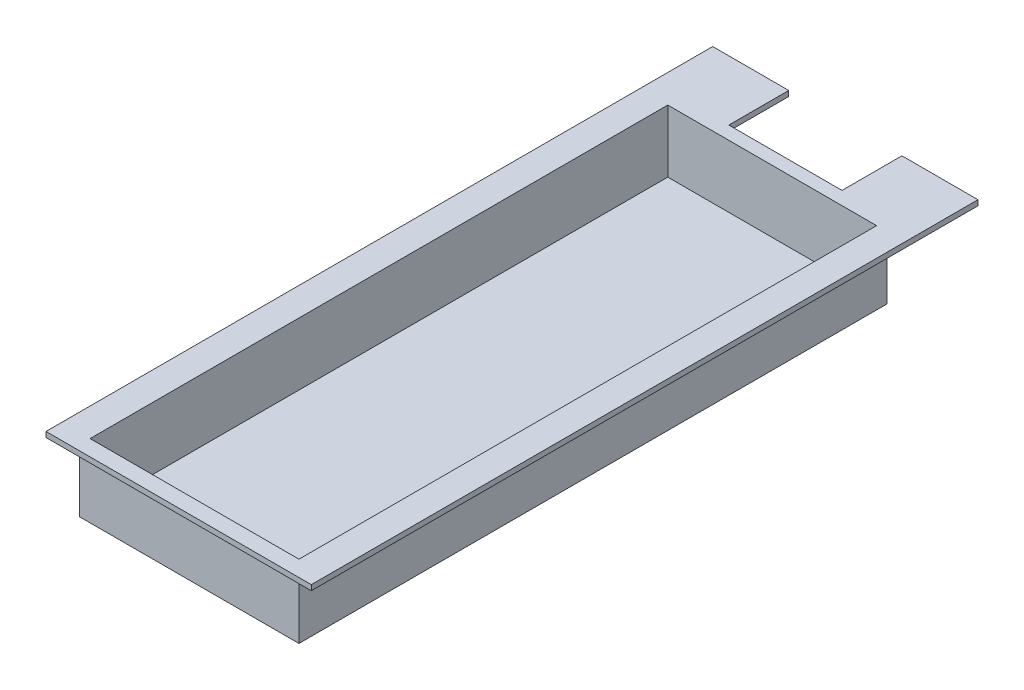
SolidWorks part; units mm, degrees
ref_plane "Front Plane" through (0, 0, 0) normal (0, 0, 1) x (1, 0, 0)
ref_plane "Top Plane" through (0, 0, 0) normal (0, 1, 0) x (1, 0, 0)
ref_plane "Right Plane" through (0, 0, 0) normal (1, 0, 0) x (0, 0, -1)
sketch "Sketch1" plane through (0, 0, 0) normal (0, 1, 0) x (1, 0, 0)
  line L2 (63.8696, 121.7466) -> (63.8696, -211.8735)
  line L3 (63.8696, -211.8735) -> (188.3296, -211.8735)
  line L4 (188.3296, 121.7466) -> (188.3296, -211.8735)
  line L7 (87.9996, 121.7466) -> (63.8696, 121.7466)
  line L8 (87.9996, 121.7466) -> (164.1996, 121.7466)
  line L11 (164.1996, 121.7466) -> (188.3296, 121.7466)
  dimension "D5" = 124.46
  dimension "D6" = 76.2
base flange "Base-Flange1" sketch "Sketch1" thickness 3 reverse thickness direction no parameters "D1"=9
ref_plane "Plane3" through (0, 0, 0) normal (0, 1, 0) x (1, 0, 0)
sketch "Sketch75" plane through (0, 0, 0) normal (0, 1, 0) x (1, 0, 0)
  line L0 (63.8696, -211.8735) -> (188.3296, -211.8735) construction
  line L2 (63.8696, 121.7466) -> (63.8696, -211.8735)
  line L3 (63.8696, -211.8735) -> (66.8696, -211.8735)
  line L5 (167.1996, 118.7466) -> (185.3296, 118.7466)
  line L6 (164.1996, 121.7466) -> (185.3296, 121.7466)
  line L8 (66.8696, -208.8735) -> (185.3296, -208.8735)
  line L10 (66.8696, -211.8735) -> (188.3296, -211.8735)
  line L11 (188.3296, -193.287) -> (188.3296, -211.8735)
  line L12 (188.3296, 121.7466) -> (63.8696, 121.7466) construction
  line L13 (84.9996, 118.7466) -> (66.8696, 118.7466)
  line L18 (87.9996, 121.7466) -> (63.8696, 121.7466)
  line L19 (66.8696, 118.7466) -> (66.8696, -208.8735)
  line L20 (188.3296, -193.287) -> (188.3296, 121.7466)
  line L21 (87.9996, 121.7466) -> (164.1996, 121.7466)
  line L23 (87.9996, 118.7466) -> (164.1996, 118.7466)
  line L25 (188.3296, 121.7466) -> (185.3296, 121.7466)
  line L29 (87.9996, 118.7466) -> (84.9996, 118.7466)
  line L35 (164.1996, 118.7466) -> (167.1996, 118.7466)
  line L48 (185.3296, 118.7466) -> (185.3296, -208.8735)
  point P4 (65.3696, -21.027)
  point P11 (127.5996, -194.787)
  point P39 (186.8296, -21.027)
  dimension "D2" = 3
  dimension "D4" = 3
extrude "Boss-Extrude1" add sketch "Sketch75" along normal blind 35.4 contours L20 L25 L6 L21 L18 L2 L3 L10 L11 L5 L48 L8 L19 L13 L29 L23 L35
ref_plane "Plane4" through (0, 35.4, 0) normal (0, 1, 0) x (1, 0, 0)
sketch "Sketch76" plane through (0, 35.4, 0) normal (0, 1, 0) x (1, 0, 0)
  line L0 (164.1996, 121.7466) -> (87.9996, 121.7466) construction
  line L3 (168.6072, 160.233) -> (188.3296, 160.233)
  line L5 (63.8696, -211.8735) -> (188.3296, -211.8735) construction
  line L6 (63.8696, 121.7466) -> (87.9996, 121.7466)
  line L7 (168.6072, 160.233) -> (158.1996, 160.233)
  line L9 (164.1996, 121.7466) -> (142.9989, 121.7466)
  line L10 (158.1996, 160.233) -> (158.1996, 126.2466)
  line L11 (164.1996, 121.7466) -> (188.3296, 121.7466)
  line L12 (63.8696, 121.7466) -> (63.8696, -211.8735)
  line L13 (188.3296, -211.8735) -> (188.3296, 121.7466)
  line L14 (158.1996, 126.2466) -> (93.9996, 126.2466)
  line L16 (142.9989, 121.7466) -> (87.9996, 121.7466)
  line L23 (93.9996, 154.233) -> (93.9996, 126.2466)
  line L28 (61.1738, 160.233) -> (93.9996, 160.233)
  line L29 (93.9996, 154.233) -> (93.9996, 160.233)
  line L32 (61.1738, 160.233) -> (50.8696, 160.233)
  line L35 (50.8696, 160.233) -> (50.8696, -212.8408)
  line L38 (50.8696, 160.233) -> (61.1738, 160.233)
  line L39 (63.8696, -211.8735) -> (188.3296, -211.8735)
  line L40 (50.8696, -212.8408) -> (50.8696, -217.8735)
  line L41 (50.8696, -217.8735) -> (190.3296, -217.8735)
  line L45 (188.3296, 160.233) -> (201.3296, 160.233)
  line L47 (190.3296, -217.8735) -> (201.3296, -217.8735)
  line L48 (201.3296, 160.233) -> (201.3296, -217.8735)
  dimension "D1" = 13
  dimension "D2" = 6
  dimension "D3" = 4.5
  dimension "D4" = 13
  dimension "D5" = 43.13
  dimension "D6" = 43.13
extrude "Boss-Extrude2" add sketch "Sketch76" against normal blind 3
sketch "Bend-Lines1" [suppressed] plane through (0, 0, 0) normal (0, 1, 0) x (1, 0, 0)
sketch "Bounding-Box1" [suppressed] plane through (0, 0, 0) normal (0, 1, 0) x (1, 0, 0)
sheet metal parameters "Sheet-Metal4" thickness 3 parameters "D1"=9
flat pattern "Flat-Pattern4" [suppressed]
sketch "Bend-Lines2" plane through (0, 0, 0) normal (0, 1, 0) x (1, 0, 0)
sketch3d "Bounding-Box2" [suppressed]
  line L0 (188.3296, 121.7466, 0) -> (188.3296, -220.767, 0) construction
  line L1 (63.8696, 121.7466, 0) -> (63.8696, -220.767, 0) construction
  line L2 (188.3296, 121.7466, 0) -> (63.8696, 121.7466, 0) construction
  line L3 (188.3296, -220.767, 0) -> (63.8696, -220.767, 0) construction
sheet metal parameters "Sheet-Metal8" thickness 3 parameters "D1"=9
flat pattern "Flat-Pattern4"
sketch "Bend-Lines2" plane through (0, 0, 0) normal (0, 1, 0) x (1, 0, 0)
sketch3d "Bounding-Box2" [suppressed]
  line L0 (188.3296, 154.233, 35.4) -> (188.3296, -220.767, 35.4) construction
  line L1 (63.8696, 154.233, 35.4) -> (63.8696, -220.767, 35.4) construction
  line L2 (188.3296, 154.233, 35.4) -> (63.8696, 154.233, 35.4) construction
  line L3 (188.3296, -220.767, 35.4) -> (63.8696, -220.767, 35.4) construction
sheet metal parameters "Sheet-Metal9" thickness 3 parameters "D1"=9
flat pattern "Flat-Pattern4"
sketch "Bend-Lines2" plane through (0, 0, 0) normal (0, 1, 0) x (1, 0, 0)
sketch3d "Bounding-Box2" [suppressed]
  line L0 (66.8696, 118.7466, 0) -> (66.8696, -208.8735, 0) construction
  line L1 (185.3296, 118.7466, 0) -> (185.3296, -208.8735, 0) construction
  line L2 (66.8696, 118.7466, 0) -> (185.3296, 118.7466, 0) construction
  line L3 (66.8696, -208.8735, 0) -> (185.3296, -208.8735, 0) construction
